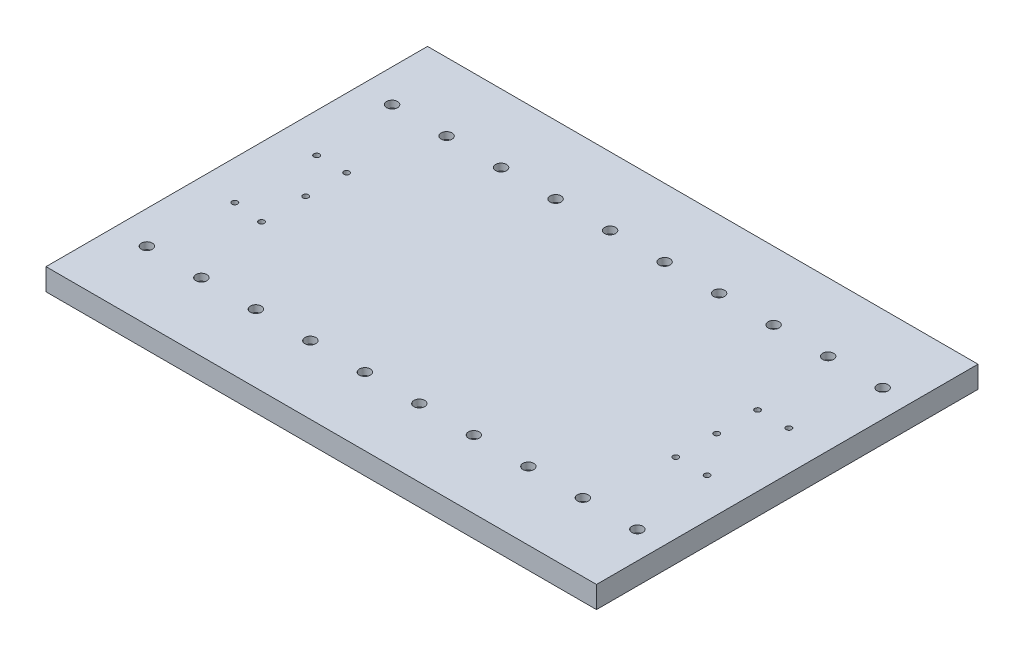
SolidWorks part; units mm, degrees
material "Plain Carbon Steel"
ref_plane "Front Plane" through (0, 0, 0) normal (0, 0, 1) x (1, 0, 0)
ref_plane "Top Plane" through (0, 0, 0) normal (0, 1, 0) x (1, 0, 0)
ref_plane "Right Plane" through (0, 0, 0) normal (1, 0, 0) x (0, 0, -1)
sketch "Sketch1" plane through (0, 0, 0) normal (1, 0, 0) x (0, 0, -1)
  line L1 (-350, -20) -> (350, -20)
  line L2 (-350, -20) -> (-350, 20)
  line L3 (-350, 20) -> (350, 20)
  line L4 (350, -20) -> (350, 20)
  line L5 (-350, -20) -> (350, 20) construction
  line L6 (-350, 20) -> (350, -20) construction
  point P0 (0, 0)
  dimension "D1" = 700
  dimension "D2" = 40
extrude "Boss-Extrude1" add sketch "Sketch1" along normal mid plane 1010
hole_wizard "M12 Tapped Hole1" positions "Sketch4" profile "Sketch3" tap size "M12" standard "ISO"
sketch "Sketch4" plane through (0, 20, 0) normal (0, 1, 0) x (1, 0, 0)
  point P0 (-378.5, 75.052)
  point P3 (-433.5, 75)
  point P6 (-378.5, -81.131)
  point P9 (-433.5, -75)
  point P12 (433, 75)
  point P15 (375.5, 75)
  point P18 (433, -75)
  point P21 (375.5, -75)
  point P24 (375.5, 0)
  point P27 (-378.5, 0)
sketch "Sketch3" plane through (-378.5, 20, -75.052) normal (1, 0, 0) x (0, 0, 1)
  line L0 (0, 0) -> (0, 32.3144)
  line L1 (0, 32.3144) -> (5.1, 29.25)
  line L2 (5.1, 29.25) -> (5.1, 0)
  line L5 (5.1, 0) -> (0, 0)
  line L10 (0, 32.3144) -> (-5.1, 29.25) construction
  line L11 (0, -6.35) -> (0, 107.95) construction
  dimension "Tap Drill Dia." = 10.2
  dimension "Tap Drill Depth" = 29.25
  dimension "Drill Angle" = 118
cosmetic thread "Hole Thread1" parameters "D1"=24, "D2"=12
cosmetic thread "Hole Thread2" parameters "D1"=24, "D2"=12
cosmetic thread "Hole Thread3" parameters "D1"=24, "D2"=12
cosmetic thread "Hole Thread4" parameters "D1"=24, "D2"=12
cosmetic thread "Hole Thread5" parameters "D1"=24, "D2"=12
cosmetic thread "Hole Thread6" parameters "D1"=24, "D2"=12
cosmetic thread "Hole Thread7" parameters "D1"=24, "D2"=12
cosmetic thread "Hole Thread8" parameters "D1"=24, "D2"=12
cosmetic thread "Hole Thread9" parameters "D1"=24, "D2"=12
cosmetic thread "Hole Thread10" parameters "D1"=24, "D2"=12
sketch "Sketch7" plane through (0, 20, 0) normal (0, 1, 0) x (1, 0, 0)
  line L0 (505, 350) -> (505, -350) construction
  line L1 (505, 0) -> (-505, 0) construction
  line L2 (-505, 350) -> (-505, -350) construction
  point P0 (455, -225)
  dimension "D1" = 50
  dimension "D2" = 225
hole_wizard "CBORE for M12 Hex Socket Head Cap Screw1" positions "Sketch7" profile "Sketch6" counterbore size "M12" standard "ISO" end condition through all
sketch "Sketch6" plane through (455, 20, 225) normal (1, 0, 0) x (0, 0, 1)
  line L0 (0, 0) -> (0, 40)
  line L1 (0, 40) -> (6.5, 40)
  line L3 (6.5, 40) -> (6.5, 12.6)
  line L4 (6.5, 12.6) -> (10, 12.6)
  line L5 (10, 12.6) -> (10, 0)
  line L7 (10, 0) -> (0, 0)
  line L11 (0, -6.35) -> (0, 107.95) construction
  dimension "Thru Hole Dia." = 13
  dimension "Thru Hole Depth" = 40
  dimension "C'Bore Dia." = 20
  dimension "C'Bore Depth" = 12.6
pattern_linear "LPattern1" count 10 spacing 100 along (-1, 0, 0) count 2 spacing 450 along (0, 0, -1) of "CBORE for M12 Hex Socket Head Cap Screw1"
